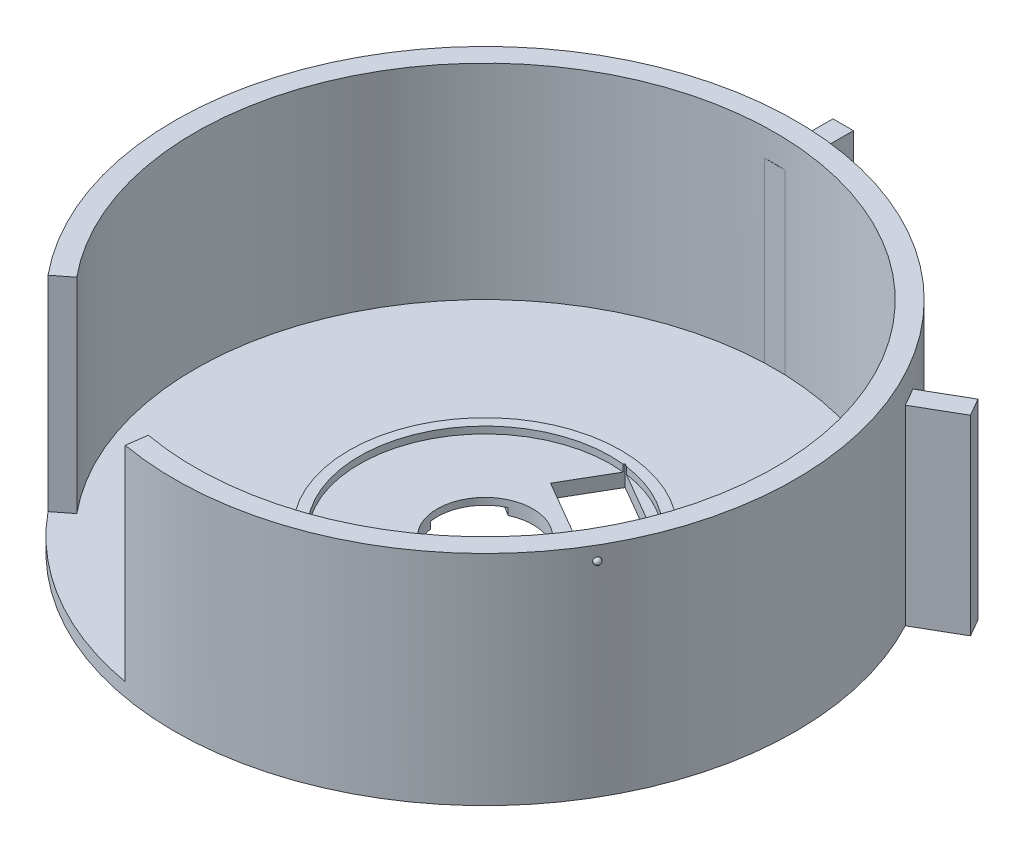
SolidWorks part; units mm, degrees
ref_plane "Front Plane" through (0, 0, 0) normal (0, 0, 1) x (1, 0, 0)
ref_plane "Top Plane" through (0, 0, 0) normal (0, 1, 0) x (1, 0, 0)
ref_plane "Right Plane" through (0, 0, 0) normal (1, 0, 0) x (0, 0, -1)
sketch "Sketch1" plane through (0, 0, 0) normal (0, 1, 0) x (1, 0, 0)
  circle A0 centre (0, 0) radius 45.5
  circle A1 centre (0, 0) radius 42.5
  dimension "D1" = 85
  dimension "D2" = 3
  dimension "D3" = 91
extrude "Boss-Extrude1" add sketch "Sketch1" along normal blind 32
sketch "Sketch2" plane through (0, 0, 0) normal (0, -1, 0) x (1, 0, 0)
  circle A0 centre (0, 0) radius 45.5
extrude "Boss-Extrude2" add sketch "Sketch2" against normal blind 2
sketch "Sketch3" plane through (0, 2, 0) normal (0, 1, 0) x (1, 0, 0)
  circle A0 centre (0, 0) radius 7
  dimension "D1" = 14
extrude "Cut-Extrude1" cut sketch "Sketch3" against normal blind 2
sketch "Sketch7" plane through (0, 2, 0) normal (0, 1, 0) x (1, 0, 0)
  line L12 (1.5, 52.4735) -> (1.5, 42.4735)
  line L13 (1.5, 52.4735) -> (-1.5, 52.4735)
  line L14 (-1.5, 52.4735) -> (-1.5, 42.4735)
  line L16 (46.1934, 24.9377) -> (37.5331, 19.9377)
  line L17 (46.1934, 24.9377) -> (44.6934, 27.5358)
  line L18 (44.6934, 27.5358) -> (36.0331, 22.5358)
  line L32 (-1.5, 42.4735) -> (1.5, 42.4735)
  line L37 (36.0331, 22.5358) -> (37.5331, 19.9377)
  circle A0 centre (0, 0) radius 42.5 construction
  point P27 (0, 0)
  dimension "D1" = 3
  dimension "D2" = 3
  dimension "D3" = 10
  dimension "D4" = 10
  dimension "D5" = 10
extrude "Boss-Extrude4" add sketch "Sketch7" along normal blind 26 and the other way blind 2
sketch "Sketch8" plane through (0, 2, 0) normal (0, 1, 0) x (1, 0, 0)
  circle A0 centre (0, 0) radius 19.8902
  circle A1 centre (0, 0) radius 18.3902
  dimension "D1" = 1.5
extrude "Boss-Extrude5" add sketch "Sketch8" along normal blind 1
sketch "Sketch10" plane through (0, 0, 0) normal (0, -1, 0) x (1, 0, 0)
  line L0 (0, -52.4735) -> (0, 8.0171) construction
  line L5 (1.5, -52.4735) -> (-1.5, -52.4735) construction
  line L8 (46.1934, -24.9377) -> (44.6934, -27.5358) construction
  line L24 (12.911, -7.4542) -> (45.4434, -26.2368) construction
  line L25 (2.0667, -18.4656) -> (15.0319, -10.9221)
  line L26 (2.0667, -18.4656) -> (-1.9565, -11.5508)
  line L27 (15.0319, -10.9221) -> (11.0087, -4.0074)
  line L28 (-1.9565, -11.5508) -> (11.0087, -4.0074)
  dimension "D1" = 15
  dimension "D2" = 8
  dimension "D3" = 9
  dimension "D4" = 7.5
extrude "Cut-Extrude4" cut sketch "Sketch10" against normal blind 5.5
sketch "Sketch11" plane through (0, 2, 0) normal (0, 1, 0) x (1, 0, 0)
  line L0 (0, 0) -> (-22.75, -39.4042) construction
  line L1 (-32.6066, -26.8741) -> (-35.1652, -28.8731)
  line L2 (-7.4952, -41.7388) -> (-7.926, -44.8043)
  line L5 (-35.1652, -28.8731) -> (-33.825, -37.7542)
  line L6 (-33.825, -37.7542) -> (-11.7383, -48.7724)
  line L7 (-11.7383, -48.7724) -> (-7.926, -44.8043)
  line L8 (-32.6066, -26.8741) -> (-25.9653, -26.8741)
  line L9 (-25.9653, -26.8741) -> (-9.9785, -35.4192)
  line L10 (-9.9785, -35.4192) -> (-7.4952, -41.7388)
  circle A0 centre (0, 0) radius 45.5 construction
  dimension "D1" = 22
  dimension "D2" = 22
extrude "Cut-Extrude5" cut sketch "Sketch11" along normal blind 58.5
sketch "Sketch12" plane through (0, 0, 0) normal (0, -1, 0) x (1, 0, 0)
  line L0 (-6.9123, 1.1048) -> (-24.2076, -9.4803)
  line L1 (-6.9123, 1.1048) -> (-2.5191, -6.0733)
  line L2 (-24.2076, -9.4803) -> (-19.8145, -16.6584)
  line L3 (-2.5191, -6.0733) -> (-19.8145, -16.6584)
  circle A0 centre (0, 0) radius 7 construction
extrude "Cut-Extrude6" cut sketch "Sketch12" against normal blind 1
ref_plane "Plane1" through (22.8316, 0, -39.2413) normal (0.5029, 0, -0.8643) x (-0.8643, 0, -0.5029)
sketch "Sketch13" plane through (22.8316, 0, -39.2413) normal (0.5029, 0, -0.8643) x (-0.8643, 0, -0.5029)
  line L7 (45.5, 32) -> (-45.5, 32) construction
  circle A0 centre (0, 30) radius 0.5
  dimension "D1" = 1
  dimension "D2" = 2
extrude "Boss-Extrude6" add sketch "Sketch13" along normal blind 0.5 and the other way blind 2 separate body
fillet "Fillet1" radius 0.5 1 edges at (22.6509, 30, -39.9249)
ref_plane "Plane4" through (39.3277, 0, 22.8819) normal (0.8643, 0, 0.5029) x (0.5029, 0, -0.8643)
sketch "Sketch23" plane through (39.3277, 0, 22.8819) normal (0.8643, 0, 0.5029) x (0.5029, 0, -0.8643)
  line L0 (45.5, 32) -> (-42.7124, 32) construction
  circle A0 centre (0, 30) radius 0.5
  point P4 (0, 30)
  dimension "D1" = 2
extrude "Boss-Extrude7" add sketch "Sketch23" along normal blind 0.5 and the other way blind 2
fillet "Fillet2" radius 0.5 1 edges at (40.0113, 30, 22.7012)
ref_plane "Plane5" through (0, 0, 0) normal (0.8643, 0, 0.5029) x (0.5029, 0, -0.8643)
mirror "Mirror1" about plane through (0, 0, 0) normal (0.8643, 0, 0.5029) of "Fillet2", "Boss-Extrude7"
